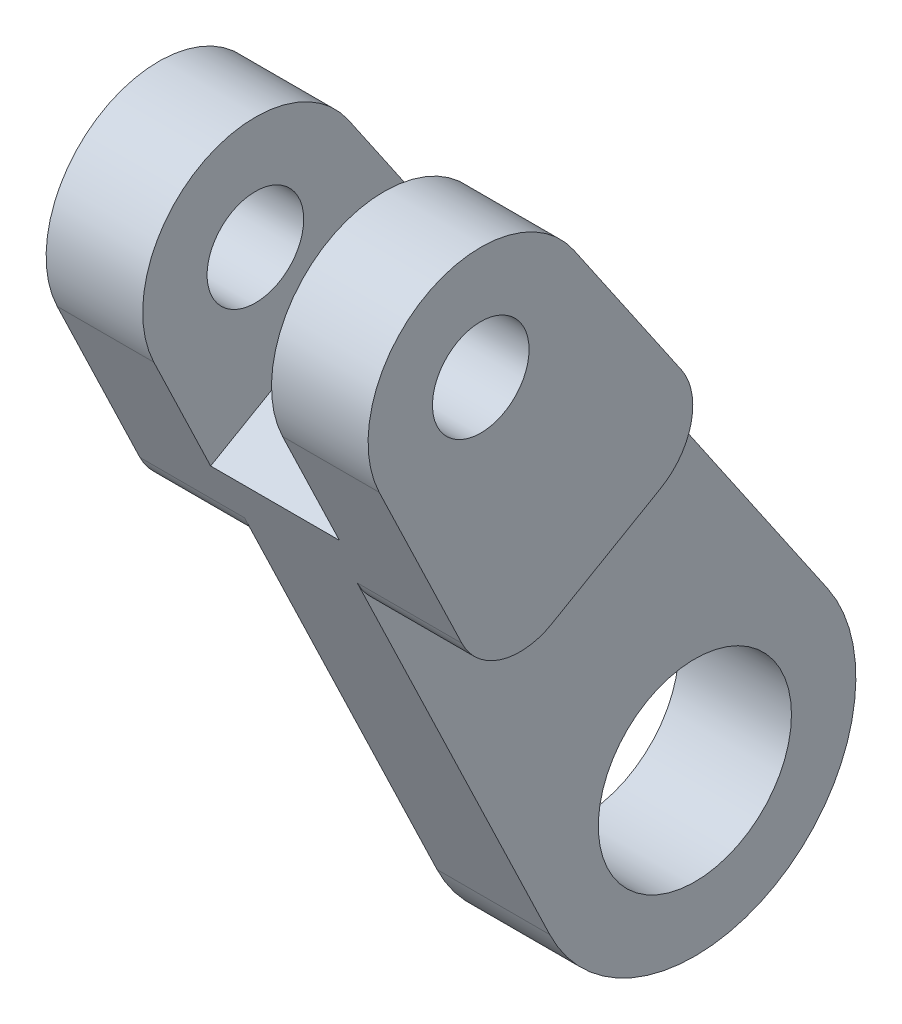
SolidWorks part; units mm, degrees
ref_plane "Front Plane" through (0, 0, 0) normal (0, 0, 1) x (1, 0, 0)
ref_plane "Top Plane" through (0, 0, 0) normal (0, 1, 0) x (1, 0, 0)
ref_plane "Right Plane" through (0, 0, 0) normal (1, 0, 0) x (0, 0, -1)
sketch "Sketch1" plane through (0, 0, 0) normal (1, 0, 0) x (0, 0, -1)
  line L0 (0, 0) -> (-9.9, 17.1473) construction
  line L1 (-7.0102, 19.1219) -> (4.1283, 2.8209)
  line L2 (-13.055, 15.632) -> (-4.5071, -2.1648)
  line L3 (-11.2899, 11.957) -> (-4.7101, 15.7558)
  line L4 (-2.447, 12.4437) -> (-9.553, 8.341)
  line L5 (0, 0) -> (0, 24.845) construction
  circle A0 centre (0, 0) radius 3
  circle A1 centre (0, 0) radius 5
  circle A2 centre (-9.9, 17.1473) radius 3.5
  circle A3 centre (-9.9, 17.1473) radius 1.5
  dimension "D1" = 3
  dimension "D2" = 7
  dimension "D4" = 6
  dimension "D5" = 2
  dimension "D3" = 4
  dimension "D6" = 12
  dimension "D7" = 23.3
  dimension "D8" = 30
extrude "Boss-Extrude1" add sketch "Sketch1" along normal blind 1.75 and the other way blind 1.75 contours A1 L1 L4 L2 | A1 A0 | L4 L1 L3 L2 region at (0, 12.1021, 6.9872) region at (0, 6.8067, 3.9299) region at (0, 1.4345, -4.642)
extrude "Boss-Extrude4" add sketch "Sketch1<5>" along normal blind 2 and the other way blind 2 contours L4 L1 L3 L2 region at (0, 12.1021, 6.9872)
sketch "Sketch1<5>" plane through (0, 0, 0) normal (1, 0, 0) x (0, 0, -1) same geometry as "Sketch1"
extrude "Boss-Extrude2" add sketch "Sketch1<3>" along normal blind 3 from surface contours L4 L1 L3 L2 | A2 L2 L3 L1 | A2 A3 region at (0, 17.3768, 5.951) region at (0, 18.1514, 6.6506) region at (0, 12.1021, 6.9872) starting at face at (2, 12.1244, 7)
sketch "Sketch1<3>" plane through (0, 0, 0) normal (1, 0, 0) x (0, 0, -1) same geometry as "Sketch1"
extrude "Boss-Extrude3" add sketch "Sketch1<4>" against normal blind 3 from surface contours A2 L2 L3 L1 | L4 L1 L3 L2 | A2 A3 region at (0, 17.3768, 5.951) region at (0, 18.1514, 6.6506) region at (0, 12.1021, 6.9872) starting at face at (-2, 12.1244, 7)
sketch "Sketch1<4>" plane through (0, 0, 0) normal (1, 0, 0) x (0, 0, -1) same geometry as "Sketch1"
fillet "Fillet2" radius 2 4 edges at (-3.375, 8.341, 9.553) (3.375, 8.341, 9.553) (-3.375, 12.4437, 2.447) (3.375, 12.4437, 2.447)
